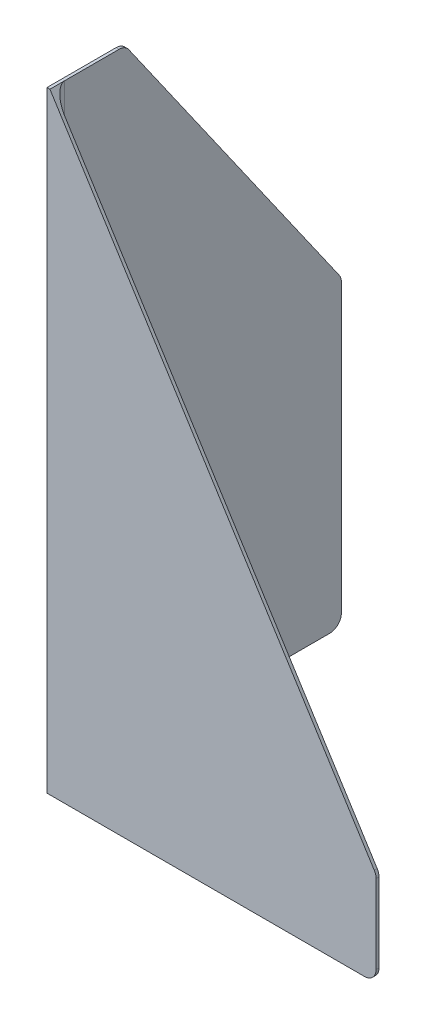
SolidWorks part; units mm, degrees
ref_plane "Front Plane" through (0, 0, 0) normal (0, 0, 1) x (1, 0, 0)
ref_plane "Top Plane" through (0, 0, 0) normal (0, 1, 0) x (1, 0, 0)
ref_plane "Right Plane" through (0, 0, 0) normal (1, 0, 0) x (0, 0, -1)
sketch "Sketch1" plane through (0, 0, 0) normal (0, 1, 0) x (1, 0, 0)
  line L0 (0, 0) -> (177.8, 0)
  line L1 (177.8, 0) -> (177.8, 1.5875)
  line L2 (177.8, 1.5875) -> (1.5875, 1.5875)
  line L3 (1.5875, 1.5875) -> (1.5875, 157.48)
  line L4 (1.5875, 157.48) -> (0, 157.48)
  line L5 (0, 157.48) -> (0, 0)
  dimension "D1" = 157.48
  dimension "D2" = 177.8
  dimension "D3" = 1.5875
  dimension "D4" = 1.5875
extrude "Boss-Extrude1" add sketch "Sketch1" along normal blind 330.2
sketch "Sketch2" plane through (0, 0, 0) normal (-1, 0, 0) x (0, 0, 1)
  line L0 (-40.64, 330.2) -> (-157.48, 163.322)
  line L1 (-157.48, 163.322) -> (-157.48, 330.2)
  line L2 (-157.48, 330.2) -> (-40.64, 330.2)
  line L3 (-157.48, 330.2) -> (-157.48, 0) construction
  line L4 (-157.48, 330.2) -> (0, 330.2) construction
  point P8 (0, 0)
  dimension "D1" = 163.322
  dimension "D2" = 40.64
extrude "Cut-Extrude1" cut sketch "Sketch2" against normal up to surface (1.5875 mm away) up to face at (1.5875, 165.1, -79.5338)
sketch "Sketch3" plane through (0, 0, 0) normal (0, 0, 1) x (1, 0, 0)
  line L0 (177.8, 330.2) -> (1.5875, 330.2)
  line L1 (1.5875, 330.2) -> (177.8, 50.8)
  line L2 (177.8, 50.8) -> (177.8, 330.2)
  line L3 (0, 330.2) -> (177.8, 330.2) construction
  line L4 (177.8, 330.2) -> (177.8, 0) construction
  line L5 (0, 330.2) -> (0, 0) construction
  dimension "D1" = 1.5875
  dimension "D2" = 50.8
extrude "Cut-Extrude2" cut sketch "Sketch3" against normal up to surface (1.5875 mm away) up to face at (89.6937, 165.1, -1.5875)
fillet "Fillet1" radius 6.35 6 edges at (177.8, 0, -0.7937) (177.8, 50.8, -0.7938) (0.7937, 0, -157.48) (0.7937, 163.322, -157.48) (1.5875, 165.1, -1.5875) (0.7937, 330.2, -40.64)
